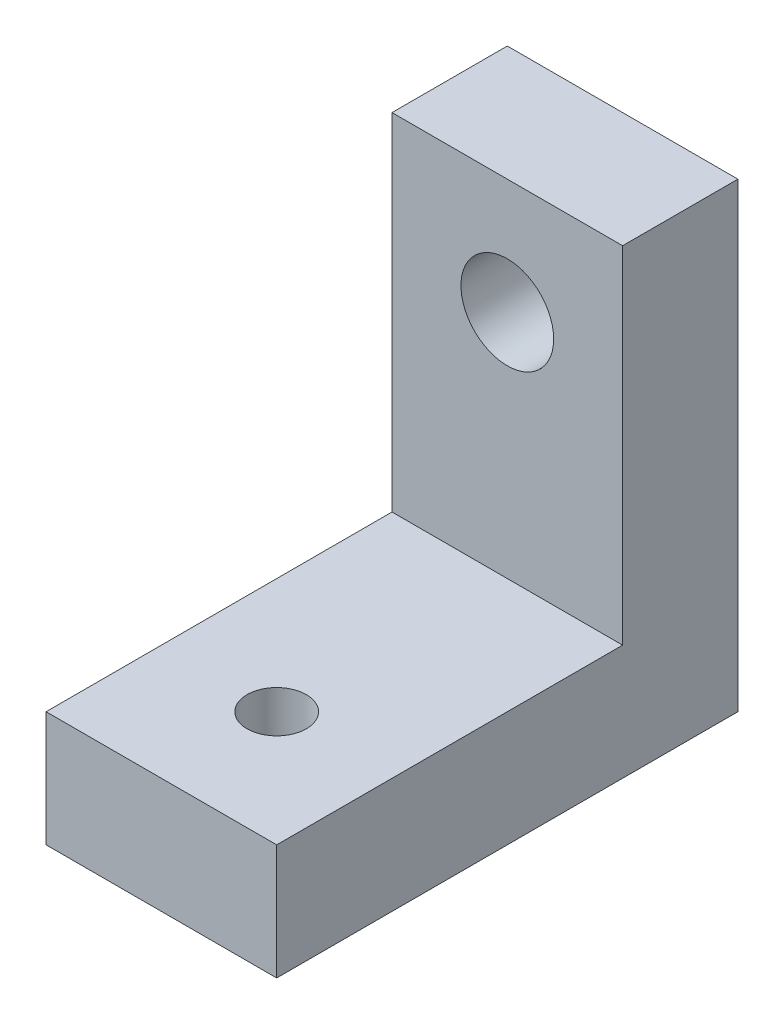
SolidWorks part; units mm, degrees
ref_plane "Front Plane" through (0, 0, 0) normal (0, 0, 1) x (1, 0, 0)
ref_plane "Top Plane" through (0, 0, 0) normal (0, 1, 0) x (1, 0, 0)
ref_plane "Right Plane" through (0, 0, 0) normal (1, 0, 0) x (0, 0, -1)
sketch "Sketch1" plane through (0, 0, 0) normal (0, 0, 1) x (1, 0, 0)
  line L0 (-6.35, 0) -> (-6.35, -19.05)
  line L1 (-6.35, -19.05) -> (6.35, -19.05)
  line L2 (6.35, -19.05) -> (6.35, 0)
  line L5 (-6.35, 0) -> (-6.35, 6.35)
  line L6 (-6.35, 6.35) -> (6.35, 6.35)
  line L7 (6.35, 0) -> (6.35, 6.35)
  circle A1 centre (0, 0) radius 2.5527
  dimension "D1" = 12.7
  dimension "D2" = 5.1054
  dimension "D3" = 25.4
  dimension "D4" = 19.05
extrude "Boss-Extrude1" add sketch "Sketch1" along normal blind 6.35
sketch "Sketch2" plane through (0, 0, 6.35) normal (0, 0, 1) x (1, 0, 0)
  line L0 (6.35, -19.05) -> (6.35, 6.35) construction
  line L1 (-6.35, -19.05) -> (6.35, -19.05)
  line L2 (-6.35, -19.05) -> (-6.35, -12.7)
  line L3 (-6.35, -12.7) -> (6.35, -12.7)
  line L4 (6.35, -19.05) -> (6.35, -12.7)
  dimension "D1" = 6.35
extrude "Boss-Extrude2" add sketch "Sketch2" along normal blind 19.05
sketch "Sketch3" plane through (0, -12.7, 0) normal (0, 1, 0) x (1, 0, 0)
  line L0 (-6.35, -25.4) -> (-6.35, -6.35) construction
  line L1 (6.35, -25.4) -> (-6.35, -25.4) construction
  circle A0 centre (0, -19.05) radius 1.632
  dimension "D1" = 3.2639
  dimension "D2" = 6.35
  dimension "D3" = 6.35
extrude "Cut-Extrude1" cut sketch "Sketch3" against normal blind 19.05
